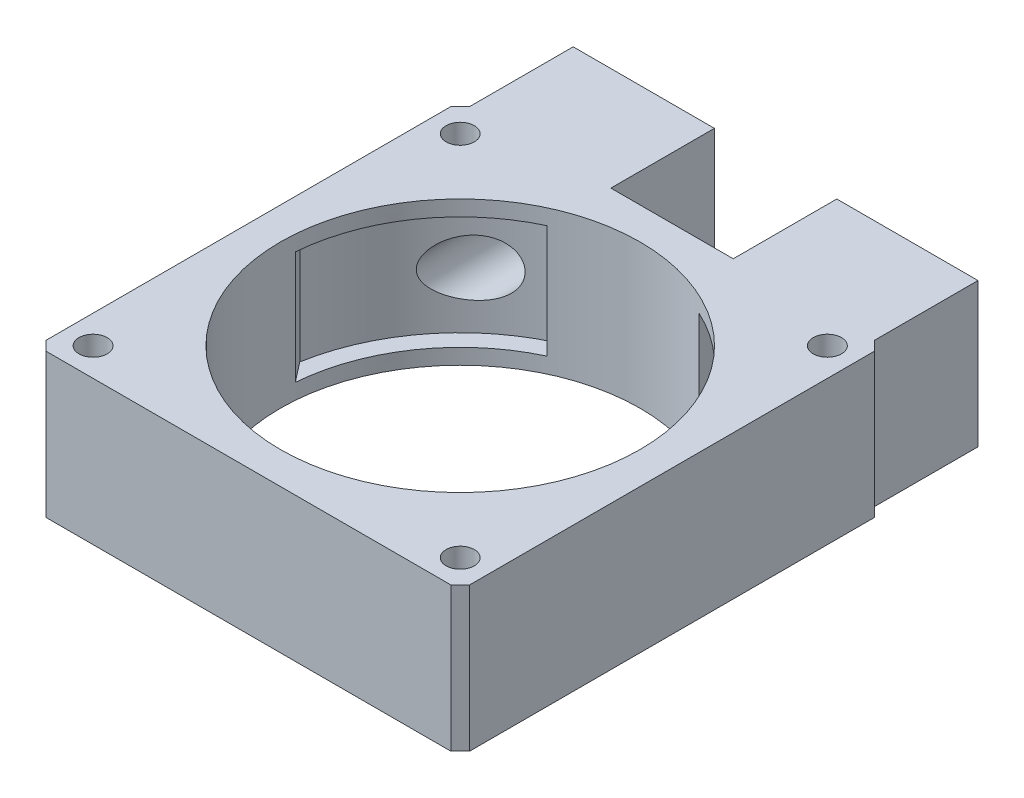
SolidWorks part; units mm, degrees
ref_plane "前视基准面" through (0, 0, 0) normal (0, 0, 1) x (1, 0, 0)
ref_plane "上视基准面" through (0, 0, 0) normal (0, 1, 0) x (1, 0, 0)
ref_plane "右视基准面" through (0, 0, 0) normal (1, 0, 0) x (0, 0, -1)
sketch "草图1" plane through (0, 0, 0) normal (0, 1, 0) x (1, 0, 0)
  line L1 (-22.5, -22.5) -> (22.5, -22.5)
  line L2 (-22.5, -22.5) -> (-22.5, 22.5)
  line L3 (-22.5, 22.5) -> (22.5, 22.5)
  line L4 (22.5, -22.5) -> (22.5, 22.5)
  line L5 (-22.5, -22.5) -> (22.5, 22.5) construction
  line L6 (-22.5, 22.5) -> (22.5, -22.5) construction
  point P0 (0, 0)
  dimension "D1" = 45
  dimension "D2" = 45
extrude "凸台-拉伸1" add sketch "草图1" along normal blind 15.3
sketch "草图2" plane through (0, 15.3, 0) normal (0, 1, 0) x (1, 0, 0)
  circle A0 centre (0, 0) radius 19.1
  dimension "D1" = 38.2
extrude "切除-拉伸1" cut sketch "草图2" against normal through all
sketch "草图3" plane through (0, 15.3, 0) normal (0, 1, 0) x (1, 0, 0)
  circle A0 centre (0, 0) radius 20
  circle A1 centre (0, 0) radius 21.5
  dimension "D1" = 40
  dimension "D2" = 43
extrude "切除-拉伸2" [suppressed] cut sketch "草图3" against normal blind 0.4
sketch "草图4" plane through (0, 0, 0) normal (0, -1, 0) x (1, 0, 0)
  circle A1 centre (0, 0) radius 21.5
  circle A2 centre (0, 0) radius 21.5
  circle A3 centre (0, 0) radius 20
  circle A4 centre (0, 0) radius 20
  dimension "D1" = 0
  dimension "D2" = 0
extrude "切除-拉伸3" [suppressed] cut sketch "草图4" against normal blind 0.4
sketch "草图5" plane through (0, 0, -22.5) normal (0, 0, -1) x (-1, 0, 0)
  line L0 (0, 15.3) -> (0, 0) construction
  line L1 (-22.5, 15.3) -> (22.5, 15.3) construction
  line L2 (-14, 15.3) -> (-14, 0) construction
  line L3 (-22.5, 0) -> (22.5, 0) construction
  line L4 (21.5, 15.3) -> (6.5, 15.3)
  line L5 (-21.5, 0) -> (-6.5, 0)
  line L6 (-21.5, 0) -> (-21.5, 15.3)
  line L7 (-21.5, 15.3) -> (-6.5, 15.3)
  line L8 (-6.5, 0) -> (-6.5, 15.3)
  line L9 (-21.5, 0) -> (-6.5, 15.3) construction
  line L10 (-21.5, 15.3) -> (-6.5, 0) construction
  line L11 (6.5, 0) -> (6.5, 15.3)
  line L12 (21.5, 0) -> (6.5, 0)
  line L13 (21.5, 0) -> (21.5, 15.3)
  point P9 (-14, 7.65)
  dimension "D1" = 15
  dimension "D2" = 14
extrude "凸台-拉伸2" add sketch "草图5" along normal blind 12
sketch "草图6" plane through (0, 0, -34.5) normal (0, 0, -1) x (-1, 0, 0)
  line L0 (-14, 15.3) -> (-14, 0) construction
  line L1 (-6.5, 15.3) -> (-21.5, 15.3) construction
  line L2 (-21.5, 0) -> (-6.5, 0) construction
  line L3 (-21.5, 7.65) -> (-6.5, 7.65) construction
  line L4 (-21.5, 15.3) -> (-21.5, 0) construction
  line L5 (-6.5, 0) -> (-6.5, 15.3) construction
  line L6 (0, 15.3) -> (0, 0) construction
  line L7 (-6.5, 15.3) -> (6.5, 15.3) construction
  circle A0 centre (-14, 7.65) radius 3
  circle A1 centre (14, 7.65) radius 3
  dimension "D1" = 6
extrude "切除-拉伸4" cut sketch "草图6" against normal blind 35
sketch "草图7" plane through (0, 15.3, 0) normal (0, 1, 0) x (1, 0, 0)
  line L0 (-21.5, 22.5) -> (-22.5, 22.5) construction
  line L1 (-22.5, 22.5) -> (-22.5, -22.5) construction
  line L2 (0, 22.5) -> (0, -22.5) construction
  line L3 (6.5, 22.5) -> (-6.5, 22.5) construction
  line L4 (-22.5, -22.5) -> (22.5, -22.5) construction
  line L5 (-22.5, 0) -> (22.5, 0) construction
  line L6 (22.5, -22.5) -> (22.5, 22.5) construction
  circle A0 centre (-19.5, 19.5) radius 1.5
  circle A1 centre (19.5, 19.5) radius 1.5
  circle A2 centre (19.5, -19.5) radius 1.5
  circle A3 centre (-19.5, -19.5) radius 1.5
  dimension "D1" = 3
  dimension "D2" = 3
  dimension "D3" = 3
extrude "切除-拉伸5" cut sketch "草图7" against normal through all
ref_plane "基准面1" through (0, 7.65, 0) normal (0, -1, 0) x (-1, 0, 0)
sketch "草图8" plane through (0, 7.65, 0) normal (0, -1, 0) x (-1, 0, 0)
  line L0 (0, 0) -> (0, 22.5) construction
  line L1 (-6.5, 22.5) -> (6.5, 22.5) construction
  line L2 (0, 0) -> (-8.875, 19.0325) construction
  line L3 (-20.681, 3.6466) -> (0, 0) construction
  line L4 (-8.875, 19.0325) -> (-8.072, 17.3105)
  line L5 (-20.681, 3.6466) -> (-18.8098, 3.3167)
  line L6 (20.681, 3.6466) -> (18.8098, 3.3167)
  line L7 (8.875, 19.0325) -> (8.072, 17.3105)
  arc A0 (-8.072, 17.3105) -> (-18.8098, 3.3167) centre (0, 0) ccw
  circle A1 centre (0, 0) radius 19.1 construction
  arc A2 (-8.875, 19.0325) -> (-20.681, 3.6466) centre (0, 0) ccw
  arc A3 (8.875, 19.0325) -> (20.681, 3.6466) centre (0, 0) cw
  arc A4 (8.072, 17.3105) -> (18.8098, 3.3167) centre (0, 0) cw
  dimension "D1" = 21
  dimension "D2" = 25
  dimension "D3" = 80
extrude "切除-拉伸6" cut sketch "草图8" against normal blind 6 and the other way blind 6
sketch "草图9" plane through (0, 0, -34.5) normal (0, 0, -1) x (-1, 0, 0)
  circle A0 centre (-14, 7.65) radius 4.25
  circle A1 centre (14, 7.65) radius 4.25
  dimension "D1" = 8.5
  dimension "D2" = 8.5
extrude "切除-拉伸7" cut sketch "草图9" against normal blind 12
chamfer "倒角1" distance 2 angle 45 2 edges at (-18.8098, 7.65, -3.3167) (18.8098, 7.65, -3.3167)
chamfer "倒角2" distance 1 angle 45 4 edges at (22.5, 7.65, 22.5) (-22.5, 7.65, 22.5) (-22.5, 7.65, -22.5) (22.5, 7.65, -22.5)
chamfer "倒角3" distance 1 angle 45 2 edges at (-18.25, 7.65, -22.5) (9.75, 7.65, -22.5)
chamfer "倒角4" distance 1 angle 45 8 edges at (-14, 0, -34.5) (-21.5, 7.65, -34.5) (-14, 15.3, -34.5) (-6.5, 7.65, -34.5) (14, 0, -34.5) (6.5, 7.65, -34.5) (14, 15.3, -34.5) (21.5, 7.65, -34.5)
